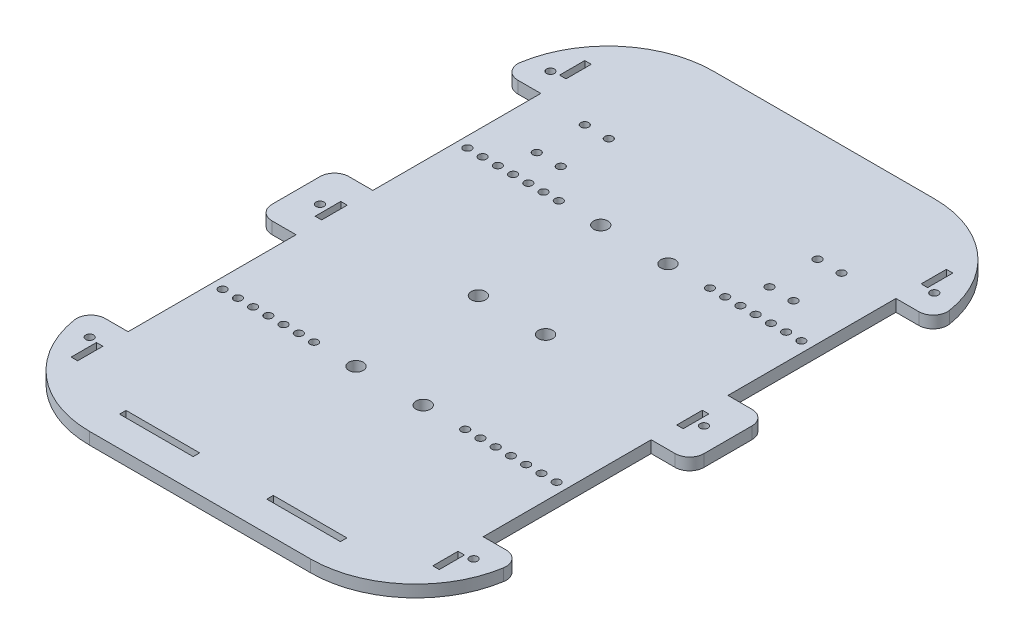
SolidWorks part; units mm, degrees
ref_plane "Ön Düzlem" through (0, 0, 0) normal (0, 0, 1) x (1, 0, 0)
ref_plane "Üst Düzlem" through (0, 0, 0) normal (0, 1, 0) x (1, 0, 0)
ref_plane "Sağ Düzlem" through (0, 0, 0) normal (1, 0, 0) x (0, 0, -1)
sketch "Sketch2" plane through (0, 0, 0) normal (0, 1, 0) x (1, 0, 0)
  line L0 (-74, -86) -> (-74, -51) construction
  line L1 (46, -130) -> (-46, -130)
  line L2 (90, -10) -> (90, 10)
  line L3 (46, 130) -> (-46, 130)
  line L4 (-90, -10) -> (-90, 10)
  line L5 (90, -130) -> (-90, 130) construction
  line L6 (90, 130) -> (-90, -130) construction
  line L7 (-83.5233, 86) -> (-74, 86)
  line L9 (-84, 16) -> (-74, 16)
  line L10 (-74, 86) -> (-74, 16)
  line L11 (-83.5233, -86) -> (-74, -86)
  line L13 (-84, -16) -> (-74, -16)
  line L14 (-74, -86) -> (-74, -16)
  line L15 (83.5233, 86) -> (74, 86)
  line L17 (84, 16) -> (74, 16)
  line L18 (74, 86) -> (74, 16)
  line L19 (83.5233, -86) -> (74, -86)
  line L21 (84, -16) -> (74, -16)
  line L22 (74, -86) -> (74, -16)
  line L23 (-74, 51) -> (74, 51) construction
  line L24 (-74, -51) -> (74, -51) construction
  line L26 (-74, 96.51) -> (-76.7, 96.51)
  line L27 (-76.7, 96.51) -> (-76.7, 107.02)
  line L28 (-74, 107.02) -> (-76.7, 107.02)
  line L29 (-74, 96.51) -> (-74, 107.02)
  line L30 (74, 96.51) -> (74, 107.02)
  line L31 (74, 107.02) -> (76.7, 107.02)
  line L32 (76.7, 96.51) -> (76.7, 107.02)
  line L33 (74, 96.51) -> (76.7, 96.51)
  line L34 (74, -107.02) -> (76.7, -107.02)
  line L35 (76.7, -96.51) -> (76.7, -107.02)
  line L36 (74, -96.51) -> (74, -107.02)
  line L37 (74, -96.51) -> (76.7, -96.51)
  line L38 (-74, -96.51) -> (-74, -107.02)
  line L39 (-74, -107.02) -> (-76.7, -107.02)
  line L40 (-76.7, -96.51) -> (-76.7, -107.02)
  line L41 (-74, -96.51) -> (-76.7, -96.51)
  line L42 (-74, 5.3333) -> (-74, -5.3333)
  line L43 (74, 5.3333) -> (74, -5.3333)
  line L44 (-74, 5.3333) -> (-76.7, 5.3333)
  line L45 (-76.7, 5.3333) -> (-76.7, -5.3333)
  line L46 (-76.7, -5.3333) -> (-74, -5.3333)
  line L47 (74, 5.3333) -> (76.7, 5.3333)
  line L48 (76.7, 5.3333) -> (76.7, -5.3333)
  line L49 (76.7, -5.3333) -> (74, -5.3333)
  line L52 (15.34, -117.53) -> (46.02, -117.53)
  line L54 (-15.34, -117.53) -> (-46.02, -117.53)
  line L56 (46.02, -117.53) -> (46.02, -114.83)
  line L57 (46.02, -114.83) -> (15.34, -114.83)
  line L59 (-15.34, -114.83) -> (-46.02, -114.83)
  line L60 (-46.02, -114.83) -> (-46.02, -117.53)
  line L62 (15.34, -117.53) -> (15.34, -114.83)
  line L63 (-15.34, -117.53) -> (-15.34, -114.83)
  arc A2 (-46, -130) -> (-89.4481, -92.9474) centre (-46, -86) cw
  arc A3 (-89.4481, 92.9474) -> (-46, 130) centre (-46, 86) cw
  arc A4 (89.4481, 92.9474) -> (46, 130) centre (46, 86) ccw
  arc A5 (89.4481, -92.9474) -> (46, -130) centre (46, -86) cw
  arc A6 (-84, 16) -> (-90, 10) centre (-84, 10) ccw
  arc A7 (-84, -16) -> (-90, -10) centre (-84, -10) cw
  arc A8 (90, 10) -> (84, 16) centre (84, 10) ccw
  arc A9 (90, -10) -> (84, -16) centre (84, -10) cw
  arc A10 (-89.4481, -92.9474) -> (-83.5233, -86) centre (-83.5233, -92) cw
  arc A11 (83.5233, -86) -> (89.4481, -92.9474) centre (83.5233, -92) cw
  arc A12 (-89.4481, 92.9474) -> (-83.5233, 86) centre (-83.5233, 92) ccw
  arc A13 (89.4481, 92.9474) -> (83.5233, 86) centre (83.5233, 92) cw
  point P0 (0, 0)
  point P34 (-90, -16)
  point P39 (90, -16)
  point P46 (-90, 86)
  point P49 (90, 86)
  dimension "D3" = 44
  dimension "D4" = 44
  dimension "D5" = 44
  dimension "D6" = 44
  dimension "D15" = 6
  dimension "D16" = 6
  dimension "D17" = 6
  dimension "D18" = 6
  dimension "D19" = 6
  dimension "D20" = 6
  dimension "D21" = 6
  dimension "D22" = 6
  dimension "D1" = 260
  dimension "D2" = 180
  dimension "D7" = 16
  dimension "D8" = 70
  dimension "D9" = 16
  dimension "D10" = 70
  dimension "D11" = 70
  dimension "D12" = 16
  dimension "D13" = 16
  dimension "D14" = 70
extrude "Boss-Extrude4" add sketch "Sketch2" along normal blind 5
sketch "Sketch5" plane through (0, 5, 0) normal (0, 1, 0) x (1, 0, 0)
  line L0 (-53.5, 63.83) -> (-43.5, 63.83) construction
  line L1 (-43.5, 63.83) -> (-43.5, 83.83) construction
  line L2 (-43.5, 83.83) -> (-43.5808, 83.8151) construction
  line L3 (-43.5808, 83.8151) -> (-53.5, 83.83) construction
  line L4 (-74, 86) -> (-74, 16) construction
  line L5 (53.5, 83.83) -> (43.5, 83.83) construction
  line L6 (43.5, 83.83) -> (43.5, 63.83) construction
  line L7 (43.5, 63.83) -> (53.5, 63.83) construction
  line L8 (74, 16) -> (74, 86) construction
  line L9 (46, 130) -> (-46, 130) construction
  circle A0 centre (-69.6, -51) radius 1.65
  circle A1 centre (-63.25, -51) radius 1.65
  circle A2 centre (-56.9, -51) radius 1.65
  circle A3 centre (-50.55, -51) radius 1.65
  circle A4 centre (-44.2, -51) radius 1.65
  circle A5 centre (-37.85, -51) radius 1.65
  circle A6 centre (-31.5, -51) radius 1.65
  circle A7 centre (31.5, -51) radius 1.65
  circle A8 centre (37.85, -51) radius 1.65
  circle A9 centre (44.2, -51) radius 1.65
  circle A10 centre (50.55, -51) radius 1.65
  circle A11 centre (56.9, -51) radius 1.65
  circle A12 centre (63.25, -51) radius 1.65
  circle A13 centre (69.6, -51) radius 1.65
  circle A14 centre (69.6, 51) radius 1.65
  circle A15 centre (63.25, 51) radius 1.65
  circle A16 centre (56.9, 51) radius 1.65
  circle A17 centre (50.55, 51) radius 1.65
  circle A18 centre (44.2, 51) radius 1.65
  circle A19 centre (37.85, 51) radius 1.65
  circle A20 centre (31.5, 51) radius 1.65
  circle A21 centre (-31.5, 51) radius 1.65
  circle A22 centre (-37.85, 51) radius 1.65
  circle A23 centre (-44.2, 51) radius 1.65
  circle A24 centre (-50.55, 51) radius 1.65
  circle A25 centre (-56.9, 51) radius 1.65
  circle A26 centre (-63.25, 51) radius 1.65
  circle A27 centre (-69.6, 51) radius 1.65
  circle A29 centre (-14, -51) radius 3
  circle A30 centre (14, -51) radius 3
  circle A31 centre (14, 51) radius 3
  circle A32 centre (-14, 51) radius 3
  circle A33 centre (-14, 0) radius 3
  circle A34 centre (14, 0) radius 3
  circle A35 centre (-80, 96) radius 1.65
  circle A36 centre (-80, 0) radius 1.65
  circle A37 centre (80, 0) radius 1.65
  circle A38 centre (-80, -96) radius 1.65
  circle A39 centre (80, -96) radius 1.65
  circle A40 centre (80, 96) radius 1.65
  circle A45 centre (-53.5, 83.83) radius 1.65
  circle A46 centre (-53.5, 63.83) radius 1.65
  circle A47 centre (-43.5, 63.83) radius 1.65
  circle A48 centre (-43.5, 83.83) radius 1.65
  circle A49 centre (43.5, 63.83) radius 1.65
  circle A50 centre (53.5, 63.83) radius 1.65
  circle A51 centre (43.5, 83.83) radius 1.65
  circle A52 centre (53.5, 83.83) radius 1.65
  dimension "D1" = 20.5
  dimension "D2" = 20.5
  dimension "D3" = 46.17
  dimension "D4" = 66.17
  dimension "D5" = 66.17
extrude "Cut-Extrude1" cut sketch "Sketch5" against normal through all
